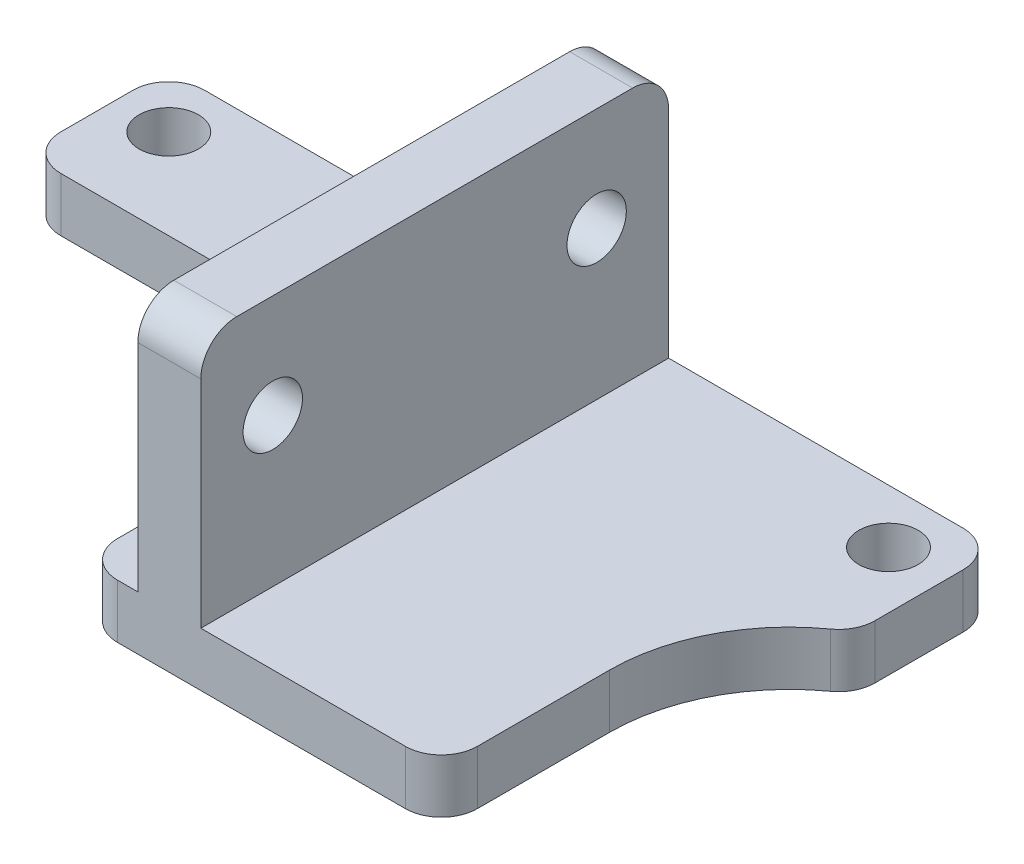
SolidWorks part; units mm, degrees
ref_plane "Front Plane" through (0, 0, 0) normal (0, 0, 1) x (1, 0, 0)
ref_plane "Top Plane" through (0, 0, 0) normal (0, 1, 0) x (1, 0, 0)
ref_plane "Right Plane" through (0, 0, 0) normal (1, 0, 0) x (0, 0, -1)
sketch "Sketch1" plane through (0, 0, 0) normal (0, 1, 0) x (1, 0, 0)
  line L0 (0, 0) -> (25, 0)
  line L1 (25, 0) -> (25, -8)
  line L2 (25, -8) -> (20, -8)
  line L3 (20, -8) -> (20, -26)
  line L4 (20, -26) -> (0, -26)
  line L5 (0, -26) -> (0, 0)
  line L6 (3.15, -3) -> (21.85, -3) construction
  line L7 (12.5, -3) -> (12.5, 0) construction
  circle A0 centre (3.15, -3) radius 1.65 construction
  circle A1 centre (21.85, -3) radius 1.65
  dimension "D6" = 3.3
  dimension "D1" = 18.7
  dimension "D2" = 25
  dimension "D3" = 20
  dimension "D4" = 8
  dimension "D5" = 26
  dimension "D7" = 3
extrude "Boss-Extrude1" add sketch "Sketch1" along normal blind 3
sketch "Sketch3" plane through (0, 3, 0) normal (0, 1, 0) x (1, 0, 0)
  line L0 (0, -26) -> (20, -26) construction
  line L1 (6.63, -26) -> (3.13, -26)
  line L2 (6.63, -26) -> (6.63, 0)
  line L3 (6.63, 0) -> (3.13, 0)
  line L4 (3.13, -26) -> (3.13, 0)
  line L5 (6.63, -26) -> (3.13, 0) construction
  line L6 (6.63, 0) -> (3.13, -26) construction
  line L7 (0, 0) -> (0, -26) construction
  point P0 (4.88, -13)
  dimension "D1" = 3.5
  dimension "D2" = 26
  dimension "D3" = 3.13
extrude "Boss-Extrude2" add sketch "Sketch3" along normal blind 14
sketch "Sketch5" plane through (0, 3, 0) normal (0, 1, 0) x (1, 0, 0)
  line L0 (25, -8) -> (25, 0) construction
  line L1 (0, 0) -> (-21.15, 0)
  line L2 (0, 0) -> (0, -8)
  line L3 (0, -8) -> (-21.15, -8)
  line L4 (-21.15, 0) -> (-21.15, -8)
  line L5 (21.85, -3) -> (-18.15, -3) construction
  circle A0 centre (-18.15, -3) radius 1.65
  circle A1 centre (21.85, -3) radius 1.65 construction
  dimension "D1" = 40
  dimension "D2" = 3
extrude "Boss-Extrude4" add sketch "Sketch5" against normal up to surface (3 mm away) up to face at (15, 0, 11.3333)
sketch "Sketch6" plane through (6.63, 0, 0) normal (1, 0, 0) x (0, 0, -1)
  line L0 (0, 11.25) -> (-26, 11.25) construction
  line L3 (-4, 11.25) -> (-4, 11.1329) construction
  line L4 (-4, 11.1329) -> (-22, 11.1329) construction
  line L5 (-22, 11.1329) -> (-22, 11.25) construction
  line L6 (-13, 11.1329) -> (-13, 17) construction
  line L7 (-26, 17) -> (0, 17) construction
  line L9 (0, 17) -> (0, 3) construction
  line L10 (-26, 17) -> (-26, 3) construction
  circle A0 centre (-4, 11.25) radius 1.65
  circle A1 centre (-22, 11.25) radius 1.65
  dimension "D2" = 3.3
  dimension "D1" = 18
  dimension "D3" = 5.75
extrude "Cut-Extrude1" cut sketch "Sketch6" against normal through all
fillet "Fillet1" radius 10 2 edges at (20, 1.5, 8) (0, 1.5, 8)
fillet "Fillet2" radius 2 8 edges at (4.88, 17, 0) (4.88, 17, 26) (0, 1.5, 26) (20, 1.5, 26) (-21.15, 1.5, 8) (-21.15, 1.5, 0) (25, 1.5, 0) (25, 1.5, 8)
sketch "Sketch7" plane through (0, 0, 0) normal (0, -1, 0) x (1, 0, 0)
  circle A1 centre (3.1539, 3) radius 1.65
  circle A2 centre (3.1539, 3) radius 1.65 construction
  circle A4 centre (3.1539, 3) radius 2.75
  dimension "D2" = 5.5
  dimension "D1" = 0
extrude "Cut-Extrude2" cut sketch "Sketch7" against normal blind 4.1
